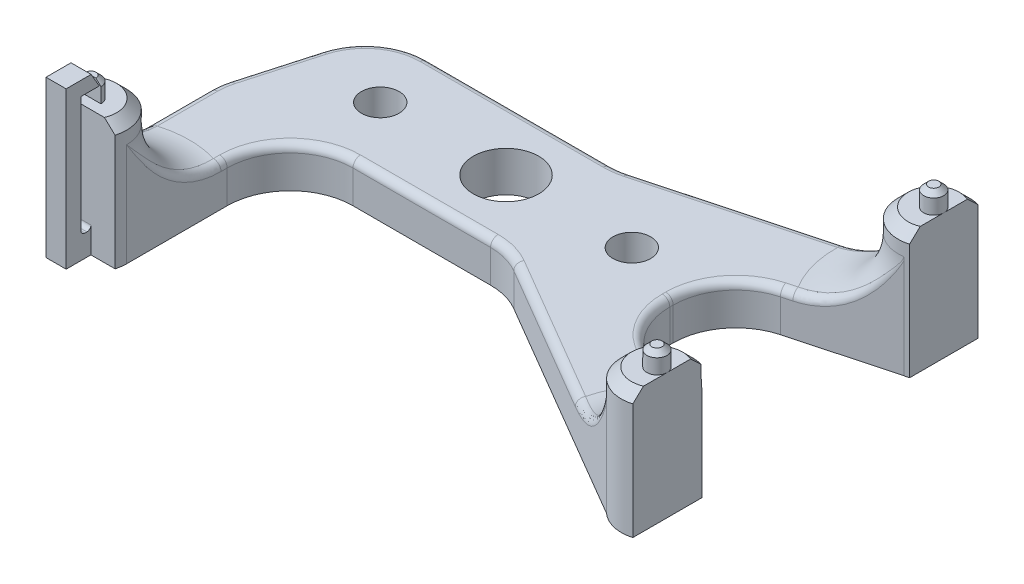
SolidWorks part; units mm, degrees
ref_plane "Front Plane" through (0, 0, 0) normal (0, 0, 1) x (1, 0, 0)
ref_plane "Top Plane" through (0, 0, 0) normal (0, 1, 0) x (1, 0, 0)
ref_plane "Right Plane" through (0, 0, 0) normal (1, 0, 0) x (0, 0, -1)
sketch "Sketch6" plane through (0, 0, 0) normal (0, 1, 0) x (1, 0, 0)
  line L1 (-19.05, -6.35) -> (19.05, -6.35)
  line L2 (-19.05, -6.35) -> (-19.05, 6.35)
  line L3 (-19.05, 6.35) -> (19.05, 6.35)
  line L4 (19.05, -6.35) -> (19.05, 6.35)
  line L5 (-19.05, -6.35) -> (19.05, 6.35) construction
  line L6 (-19.05, 6.35) -> (19.05, -6.35) construction
  point P0 (0, 0)
  dimension "D1" = 12.7
  dimension "D2" = 38.1
extrude "Boss-Extrude6" add sketch "Sketch6" along normal blind 3.175 separate body
sketch "Sketch4" plane through (0, 0, 0) normal (0, 1, 0) x (1, 0, 0)
  circle A0 centre (-19.05, -22.86) radius 3.6
  circle A1 centre (33.02, -17.78) radius 3.6
  circle A2 centre (33.02, 10.16) radius 3.6
  dimension "D1" = 7.2
  dimension "D2" = 7.2
  dimension "D3" = 7.2
  dimension "D4" = 52.07
  dimension "D5" = 5.08
  dimension "D6" = 27.94
  dimension "D7" = 10.16
  dimension "D8" = 33.02
extrude "Boss-Extrude5" add sketch "Sketch4" along normal blind 12.7
sketch "Sketch8" plane through (0, 0, 0) normal (0, 1, 0) x (1, 0, 0)
  line L2 (31.8384, 13.5606) -> (5.0632, 6.35)
  line L3 (19.05, 6.35) -> (-19.05, 6.35) construction
  line L4 (33.5862, 6.6048) -> (19.05, 2.6902)
  line L5 (19.05, -6.35) -> (19.05, 6.35) construction
  line L6 (19.05, 2.6902) -> (19.05, -6.35)
  line L7 (19.05, -6.35) -> (34.6277, -14.5589)
  line L8 (30.6114, -20.4556) -> (6.515, -6.35)
  line L9 (-19.05, -6.35) -> (19.05, -6.35) construction
  line L10 (6.515, -6.35) -> (-15.45, -6.35)
  line L11 (-15.45, -6.35) -> (-15.45, -22.86)
  line L12 (-22.65, -22.86) -> (-22.65, -6.35)
  line L13 (-22.65, -6.35) -> (-19.05, 6.35)
  line L14 (-19.05, 6.35) -> (5.0632, 6.35)
  circle A0 centre (33.02, 10.16) radius 3.6 construction
  arc A1 (33.5862, 6.6048) -> (31.8384, 13.5606) centre (33.02, 10.16) ccw
  circle A2 centre (33.02, -17.78) radius 3.6 construction
  arc A3 (34.6277, -14.5589) -> (30.6114, -20.4556) centre (33.02, -17.78) cw
  circle A4 centre (-19.05, -22.86) radius 3.6 construction
  arc A5 (-15.45, -22.86) -> (-22.65, -22.86) centre (-19.05, -22.86) cw
extrude "Boss-Extrude7" add sketch "Sketch8" along normal blind 4.064
fillet "Fillet1" radius 6.35 7 edges at (-15.45, 2.032, 6.35) (6.515, 2.032, 6.35) (19.05, 2.032, 6.35) (19.05, 2.032, -2.6902) (5.0632, 2.032, -6.35) (-22.65, 2.032, 6.35) (-19.05, 2.032, -6.35)
sketch "Sketch9" plane through (0, 4.064, 0) normal (0, 1, 0) x (1, 0, 0)
  circle A0 centre (-12.7, 0) radius 1.905
  circle A1 centre (12.7, 0) radius 1.905
  circle A2 centre (0, 0) radius 3.302
  dimension "D3" = 3.81
  dimension "D4" = 3.81
  dimension "D5" = 6.604
  dimension "D1" = 25.4
  dimension "D2" = 12.7
extrude "Cut-Extrude3" cut sketch "Sketch9" against normal through all
fillet "Fillet2" radius 6.35 3 edges at (-19.05, 4.064, 19.26) (30.0446, 4.064, 15.7534) (29.5285, 4.064, -9.2827)
chamfer "Chamfer1" distance 1.016 angle 45 3 edges at (33.02, 12.7, -6.56) (33.02, 12.7, 21.38) (-19.05, 12.7, 26.46)
fillet "Fillet3" radius 0.762 23 edges at (34.1822, 9.6509, 14.3242) (24.4655, 4.064, 9.2038) (33.042, 9.2814, -6.4582) (24.3677, 4.064, -4.1223) (20.3598, 4.064, -1.6865) (19.05, 4.064, 2.3472) (30.8667, 8.8079, -13.2989) (14.5002, 4.064, -8.8914) (5.0559, 4.064, -6.4048) (-22.65, 5.6615, 18.3911) (-22.65, 4.064, 10.4084) (-22.5895, 4.064, 6.3584) (-21.3842, 4.064, 1.8845) (-18.079, 4.064, -5.0655) (-15.45, 5.6615, 18.3911) (-15.45, 4.064, 13.142) (-13.5901, 4.064, 8.2099) (29.7882, 8.4666, 19.9737) (15.605, 4.064, 11.6711) (6.455, 4.064, 6.5713) (19.9631, 4.064, 5.7991) (-5.0133, 4.064, -6.35) (-2.1535, 4.064, 6.35)
sketch "Sketch10" plane through (0, 12.7, 0) normal (0, 1, 0) x (1, 0, 0)
  circle A0 centre (-19.05, -22.86) radius 1.016
  circle A1 centre (33.02, 10.16) radius 1.016
  circle A2 centre (33.02, -17.78) radius 1.016
  dimension "D1" = 2.032
  dimension "D2" = 2.032
  dimension "D3" = 2.032
extrude "Boss-Extrude8" add sketch "Sketch10" along normal blind 2
chamfer "Chamfer2" distance 0.5 angle 45 3 edges at (-19.05, 14.7, 23.876) (33.02, 14.7, -9.144) (33.02, 14.7, 18.796)
sketch "Sketch11" plane through (0, 12.7, 0) normal (0, 1, 0) x (1, 0, 0)
  line L1 (42.3954, 15.2971) -> (34.036, 15.2971)
  line L2 (42.3954, 15.2971) -> (42.3954, -22.8259)
  line L3 (42.3954, -22.8259) -> (34.036, -22.8259)
  line L4 (34.036, 15.2971) -> (34.036, -22.8259)
  line L5 (-24.4234, -27.7263) -> (-13.2095, -27.7263)
  line L6 (-24.4234, -27.7263) -> (-24.4234, -23.876)
  line L7 (-24.4234, -23.876) -> (-13.2095, -23.876)
  line L8 (-13.2095, -27.7263) -> (-13.2095, -23.876)
  circle A0 centre (33.02, -17.78) radius 1.016 construction
  circle A1 centre (-19.05, -22.86) radius 1.016 construction
extrude "Cut-Extrude5" cut sketch "Sketch11" against normal through all
sketch "Sketch12" plane through (0, 0, 23.876) normal (0, 0, 1) x (1, 0, 0)
  line L0 (-19.05, 12.7) -> (-19.05, 0) construction
  line L1 (-15.5963, 0) -> (-22.5037, 0) construction
  line L3 (-20.066, 0) -> (-18.034, 0)
  line L4 (-20.066, 0) -> (-20.066, 12.7)
  line L5 (-20.066, 12.7) -> (-18.034, 12.7)
  line L6 (-18.034, 0) -> (-18.034, 12.7)
  line L7 (-20.066, 0) -> (-18.034, 12.7) construction
  line L8 (-20.066, 12.7) -> (-18.034, 0) construction
  point P5 (-19.05, 6.35)
extrude "Boss-Extrude9" add sketch "Sketch12" along normal blind 4
sketch "Sketch15" plane through (0, 12.7, 0) normal (0, 1, 0) x (1, 0, 0)
  line L0 (-20.066, -23.876) -> (-21.4259, -23.876) construction
  line L1 (-20.6438, -23.876) -> (-17.3662, -23.876)
  line L2 (-20.6438, -23.876) -> (-20.6438, -22.86)
  line L3 (-20.6438, -22.86) -> (-17.3662, -22.86)
  line L4 (-17.3662, -23.876) -> (-17.3662, -22.86)
  line L5 (-19.566, -22.86) -> (-18.534, -22.86) construction
  circle A1 centre (-19.05, -22.86) radius 0.516 construction
sketch "Sketch13" plane through (-20.066, 0, 0) normal (-1, 0, 0) x (0, 0, 1)
  line L0 (27.876, 12.7) -> (23.876, 12.7) construction
  line L1 (23.876, 12.7) -> (24.876, 12.7)
  line L2 (23.876, 12.7) -> (23.876, 2.2116)
  line L3 (23.876, 2.2116) -> (24.876, 2.2116)
  line L4 (24.876, 12.7) -> (24.876, 2.2116)
  line L5 (27.876, 0) -> (26.376, 0)
  line L6 (27.876, 0) -> (27.876, 12.7)
  line L7 (27.876, 12.7) -> (26.376, 12.7)
  line L8 (26.376, 0) -> (26.376, 12.7)
  dimension "D1" = 1.5
  dimension "D2" = 1
extrude "Cut-Extrude6" cut sketch "Sketch13" against normal through all
fillet "Fillet4" radius 0.4 2 edges at (-19.05, 2.2116, 24.876) (-19.05, 2.2116, 23.876)
extrude "Cut-Extrude8" cut sketch "Sketch15" along normal through all
sketch "Sketch16" plane through (-20.066, 0, 0) normal (-1, 0, 0) x (0, 0, 1)
  line L0 (24.876, 12.7) -> (24.876, 14.35)
  line L1 (24.876, 14.35) -> (23.0317, 14.35)
  line L2 (23.0317, 14.35) -> (23.8516, 15.77)
  line L3 (23.8516, 15.77) -> (26.376, 15.77)
  line L4 (26.376, 15.77) -> (26.376, 12.7)
  line L11 (26.376, 12.7) -> (24.876, 12.7)
  line L12 (24.876, 12.7) -> (24.876, 2.6116)
  line L13 (24.476, 2.2116) -> (24.276, 2.2116)
  line L14 (23.876, 2.6116) -> (23.876, 0)
  line L15 (23.876, 0) -> (26.376, 0)
  line L16 (26.376, 0) -> (26.376, 12.7)
  line L18 (24.876, 12.7) -> (24.876, 2.6116)
  line L19 (24.476, 2.2116) -> (24.276, 2.2116)
  line L20 (23.876, 2.6116) -> (23.876, 0)
  line L21 (23.876, 0) -> (26.376, 0)
  line L22 (26.376, 0) -> (26.376, 12.7)
  arc A2 (24.476, 2.2116) -> (24.876, 2.6116) centre (24.476, 2.6116) ccw
  arc A3 (23.876, 2.6116) -> (24.276, 2.2116) centre (24.276, 2.6116) ccw
  arc A4 (24.476, 2.2116) -> (24.876, 2.6116) centre (24.476, 2.6116) ccw
  arc A5 (23.876, 2.6116) -> (24.276, 2.2116) centre (24.276, 2.6116) ccw
  point P12 (24.0595, 15.6276)
  dimension "D1" = 1.65
  dimension "D3" = 60
  dimension "D2" = 0
extrude "Boss-Extrude11" add sketch "Sketch16" against normal up to surface (2.032 mm away) up to face at (-18.034, 4.3601, 24.876)
